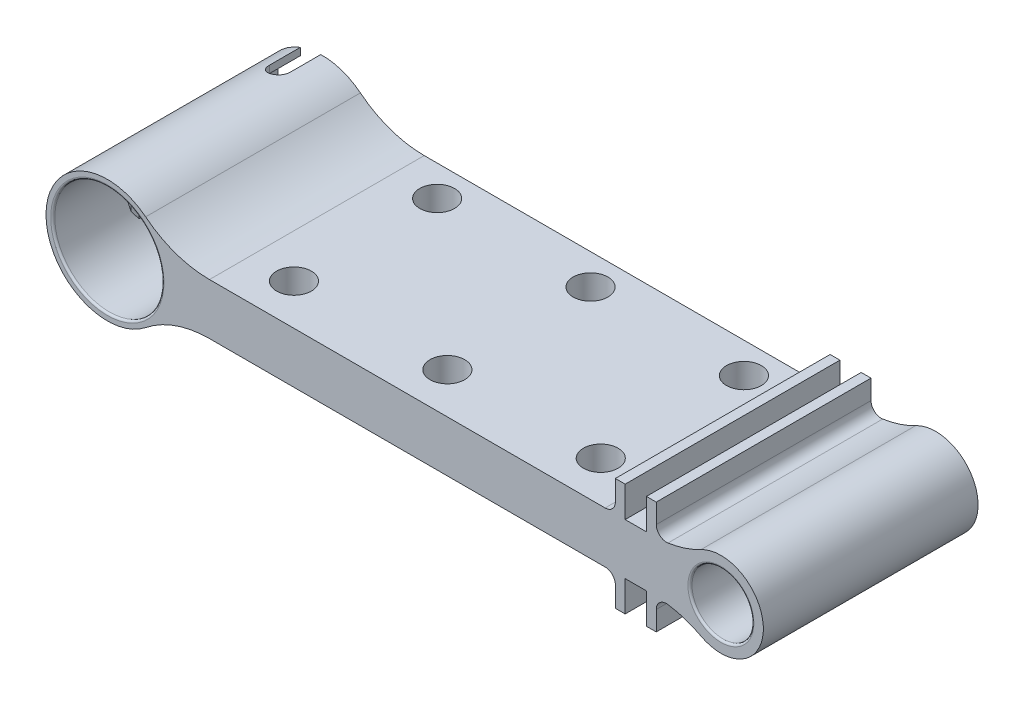
SolidWorks part; units mm, degrees
ref_plane "Front Plane" through (0, 0, 0) normal (0, 0, 1) x (1, 0, 0)
ref_plane "Top Plane" through (0, 0, 0) normal (0, 1, 0) x (1, 0, 0)
ref_plane "Right Plane" through (0, 0, 0) normal (1, 0, 0) x (0, 0, -1)
sketch "Sketch1" plane through (0, 0, 0) normal (0, 0, 1) x (1, 0, 0)
  line L0 (-35, 0) -> (35, 0) construction
  line L1 (35, -6) -> (-35, -6) construction
  line L2 (35, -6) -> (35, 6) construction
  line L3 (35, 6) -> (-35, 6) construction
  line L4 (-35, -6) -> (-35, 6) construction
  line L5 (35, -6) -> (-35, 6) construction
  line L6 (35, 6) -> (-35, -6) construction
  line L8 (-23.4456, -2.5) -> (31.1, -2.5)
  line L10 (-23.4456, 2.5) -> (31.1, 2.5)
  line L12 (-23.1971, -1.8647) -> (31.1, 2.5) construction
  line L13 (-23.1971, 1.8647) -> (31.1, -2.5) construction
  circle A0 centre (-28.9, 0) radius 5.34 construction
  arc A1 (-23.4456, 2.5) -> (-23.4456, -2.5) centre (-28.9, 0) ccw
  arc A2 (31.1, -2.5) -> (31.1, 2.5) centre (31.1, 0) ccw
  point P0 (0, 0)
  point P13 (0, 0)
  dimension "D3" = 10.68
  dimension "D5" = 5
  dimension "D1" = 70
  dimension "D2" = 12
  dimension "D4" = 6.1
  dimension "D6" = 60
extrude "Boss-Extrude1" add sketch "Sketch1" along normal blind 21 contours A1 L8 A2 L10
sketch "Sketch2" plane through (0, 0, 21) normal (0, 0, 1) x (1, 0, 0)
  circle A0 centre (-28.9, 0) radius 5.34
  dimension "D1" = 10.68
extrude "Cut-Extrude1" cut sketch "Sketch2" against normal blind 7
sketch "Sketch3" plane through (0, 0, 14) normal (0, 0, 1) x (1, 0, 0)
  line L0 (-34.24, 0) -> (-23.56, 0) construction
  line L2 (-33.19, -10) -> (-37.19, -10)
  line L3 (-33.19, -10) -> (-33.19, 10)
  line L4 (-33.19, 10) -> (-37.19, 10)
  line L5 (-37.19, -10) -> (-37.19, 10)
  line L6 (-33.19, -10) -> (-37.19, 10) construction
  line L7 (-33.19, 10) -> (-37.19, -10) construction
  line L8 (-20.61, -10) -> (-24.61, -10)
  line L9 (-20.61, -10) -> (-20.61, 10)
  line L10 (-20.61, 10) -> (-24.61, 10)
  line L11 (-24.61, -10) -> (-24.61, 10)
  line L12 (-20.61, -10) -> (-24.61, 10) construction
  line L13 (-20.61, 10) -> (-24.61, -10) construction
  line L14 (-24.61, -10) -> (-33.19, -10) construction
  line L15 (-24.61, -10) -> (-24.61, 10) construction
  line L16 (-24.61, 10) -> (-33.19, 10) construction
  line L17 (-33.19, -10) -> (-33.19, 10) construction
  line L18 (-24.61, -10) -> (-33.19, 10) construction
  line L19 (-24.61, 10) -> (-33.19, -10) construction
  circle A0 centre (-28.9, 0) radius 5.34
  point P5 (-35.19, 0)
  point P10 (-22.61, 0)
  circle M1 centre (-28.9, 0) radius 5.34
  dimension "D6" = 10.68
  dimension "D1" = 20
  dimension "D2" = 4
  dimension "D3" = 4
  dimension "D4" = 8.58
extrude "Cut-Extrude2" cut sketch "Sketch3" against normal through all contours L11 L3 M1 region at (-28.9, 0, 14)
chamfer "Chamfer1" distance 0.4 angle 45 2 edges
fillet "Fillet1" radius 10 2 edges at (-23.4456, -2.5, 10.5) (-23.4456, 2.5, 10.5)
ref_plane "Plane1" through (0, 0, 0) normal (0, 1, 0) x (1, 0, 0)
sketch "Sketch4" plane through (0, 0, 0) normal (0, 1, 0) x (1, 0, 0)
  line L0 (-25.1547, 0) -> (-34.9, 0) construction
  line L1 (-29.0273, -4) -> (-31.0273, -4)
  line L2 (-29.0273, -4) -> (-29.0273, 4)
  line L3 (-29.0273, 4) -> (-31.0273, 4)
  line L4 (-31.0273, -4) -> (-31.0273, 4)
  line L5 (-29.0273, -4) -> (-31.0273, 4) construction
  line L6 (-29.0273, 4) -> (-31.0273, -4) construction
  circle A0 centre (-30.0273, -3) radius 1
  point P0 (-30.0273, 0)
  dimension "D3" = 1
  dimension "D1" = 8
  dimension "D2" = 2
extrude "Cut-Extrude3" cut sketch "Sketch4" along normal mid plane 16.25 contours A0 | A0 L2 L3 L4 region at (-30.0273, 0, 3) region at (-30.0273, 0, -0.8887)
sketch "Sketch6" plane through (0, 0, 21) normal (0, 0, 1) x (1, 0, 0)
  circle A0 centre (31.1, 0) radius 4.15
  dimension "D1" = 8.3
extrude "Boss-Extrude2" add sketch "Sketch6" against normal through all contours A0
fillet "Fillet2" radius 10 2 edges at (27.7875, -2.5, 10.5) (27.7875, 2.5, 10.5)
sketch "Sketch5" plane through (0, 0, 0) normal (0, 0, -1) x (-1, 0, 0)
  circle A0 centre (-31.1, 0) radius 1.5
  circle A2 centre (-6.1, 0) radius 1.5
  circle A3 centre (18.9, 0) radius 1.5
  dimension "D1" = 3
  dimension "D2" = 3
extrude "Cut-Extrude5" cut sketch "Sketch5" against normal blind 4.2
sketch "Sketch7" plane through (0, 0, 21) normal (0, 0, 1) x (1, 0, 0)
  circle A0 centre (31.1, 0) radius 3.025
  dimension "D1" = 6.05
extrude "Cut-Extrude6" cut sketch "Sketch7" against normal blind 9
fillet "Fillet3" radius 0.2 2 edges at (34.125, 0, 21) (-23.56, 0, 21)
sketch "Sketch8" plane through (0, 0, 21) normal (0, 0, 1) x (1, 0, 0)
  line L0 (-18.9125, 2.5) -> (24.4688, 2.5) construction
  line L1 (20.7782, 2.5) -> (24.7782, 2.5) construction
  line L2 (20.7782, 2.5) -> (20.7782, 6.5)
  line L3 (20.7782, 6.5) -> (24.7782, 6.5) construction
  line L4 (24.7782, 2.5) -> (24.7782, 6.5)
  line L5 (22.7782, 6.5) -> (22.7782, 2.5) construction
  line L6 (20.7782, 6.5) -> (21.7382, 6.5)
  line L7 (23.8182, 2.5) -> (21.7382, 2.5) construction
  line L8 (23.8182, 2.5) -> (23.8182, 6.5)
  line L9 (23.8182, 6.5) -> (21.7382, 6.5) construction
  line L10 (21.7382, 2.5) -> (21.7382, 6.5)
  line L11 (23.8182, 2.5) -> (21.7382, 6.5) construction
  line L12 (23.8182, 6.5) -> (21.7382, 2.5) construction
  line L13 (23.8182, 6.5) -> (24.7782, 6.5)
  line L14 (20.7782, 2.5) -> (21.7382, 2.5)
  line L15 (21.7382, 2.5) -> (21.7557, 2.524)
  line L16 (23.8182, 2.5) -> (24.7782, 2.5)
  line L17 (24.7782, 2.5) -> (24.7592, 2.5837)
  line L19 (20.7782, -6.5) -> (20.7782, -2.5)
  line L20 (20.7782, -2.5) -> (21.7382, -2.5)
  line L21 (23.8182, -6.5) -> (23.8182, -2.5)
  line L22 (21.7382, -6.5) -> (21.7382, -2.5)
  line L23 (20.7782, -6.5) -> (21.7382, -6.5)
  line L24 (21.7382, -6.5) -> (21.7557, -6.476)
  line L25 (23.8182, -6.5) -> (24.7782, -6.5)
  line L26 (24.7782, -6.5) -> (24.7592, -6.4163)
  line L27 (20.7782, -6.5) -> (24.7782, -6.5) construction
  line L28 (22.7782, -2.5) -> (22.7782, -6.5) construction
  line L29 (23.8182, -6.5) -> (21.7382, -6.5) construction
  line L30 (23.8182, -2.5) -> (21.7382, -2.5) construction
  line L31 (23.8182, -6.5) -> (21.7382, -2.5) construction
  line L32 (23.8182, -2.5) -> (21.7382, -6.5) construction
  line L33 (23.8182, -2.5) -> (24.7782, -2.5)
  line L34 (24.7782, -6.5) -> (24.7782, -2.5)
  point P8 (2.7782, 2.5)
  point P9 (22.7782, 4.5)
  point P26 (22.7782, -4.5)
  line M3 (-18.9125, -2.5) -> (24.4688, -2.5)
  arc M4 (24.4688, -2.5) -> (29.1552, -3.6661) centre (24.4688, -12.5) cw
  arc M6 (29.1552, 3.6661) -> (24.4688, 2.5) centre (24.4688, 12.5) cw
  line M7 (24.4688, 2.5) -> (-18.9125, 2.5)
  dimension "D3" = 4
  dimension "D1" = 4
  dimension "D2" = 20
  dimension "D4" = 2.08
  dimension "D5" = 2
extrude "Boss-Extrude3" add sketch "Sketch8" against normal through all contours L10 L6 L2 M7 | L13 L8 L4 M7 M6 | L19 L23 L22 M3 | L34 L21 L25 M4 M3 region at (24.2981, 4.5003, 21) region at (21.2582, 4.5, 21) region at (24.2981, -4.5003, 21) region at (21.2582, -4.5, 21)
fillet "Fillet4" radius 1 4 edges at (24.7782, 2.5048, 10.5) (20.7782, 2.5, 10.5) (24.7782, -2.5048, 10.5) (20.7782, -2.5, 10.5)
sketch "Sketch10" plane through (0, 2.5, 0) normal (0, 1, 0) x (1, 0, 0)
  line L0 (-18.9125, -21) -> (19.7782, -21) construction
  line L2 (-14.6488, -17) -> (19.7782, -17) construction
  line L3 (19.7782, -21) -> (19.7782, 0) construction
  circle A0 centre (-14.6488, -17) radius 1.7
  circle A1 centre (0.3512, -17) radius 1.7
  circle A2 centre (15.3512, -17) radius 1.7
  circle A3 centre (0.3512, -3) radius 1.7
  circle A4 centre (15.3512, -3) radius 1.7
  circle A5 centre (-14.6488, -3) radius 1.7
  dimension "D2" = 4
  dimension "D5" = 2
  dimension "D1" = 3.4
  dimension "D4" = 3
extrude "Cut-Extrude7" cut sketch "Sketch10" against normal through all contours A5 | A3 | A1 L2 | L2 A2 | A2 L2 | L2 A1 | A4 | A0 region at (15.3512, 2.5, 16.2785) region at (15.3512, 2.5, 17.7215) region at (0.3512, 2.5, 16.2785) region at (0.3512, 2.5, 17.7215) region at (0.3512, 2.5, 3) region at (15.3512, 2.5, 3) region at (-14.6488, 2.5, 3)
sketch "Sketch12" plane through (0, 0, 21) normal (0, 0, 1) x (1, 0, 0)
  line L0 (24.7782, 3.5958) -> (24.7782, 6.5) construction
  line L1 (20.7782, 6.5) -> (24.7782, 6.5)
  line L2 (20.7782, 6.5) -> (20.7782, 5.5)
  line L3 (20.7782, 5.5) -> (24.7782, 5.5)
  line L4 (24.7782, 6.5) -> (24.7782, 5.5)
  line L5 (24.7782, -6.5) -> (24.7782, -3.5958) construction
  line L6 (20.7782, -6.5) -> (24.7782, -6.5)
  line L7 (20.7782, -6.5) -> (20.7782, -5.5)
  line L8 (20.7782, -5.5) -> (24.7782, -5.5)
  line L9 (24.7782, -6.5) -> (24.7782, -5.5)
  dimension "D1" = 1
  dimension "D2" = 1
extrude "Cut-Extrude8" cut sketch "Sketch12" against normal through all
equation "\"MotorDiameter\"= 10.68'I've added 0.48mm to compesate for my printer tolorance"
equation "\"D3@Sketch1\"=\"MotorDiameter\""
equation "\"D1@Sketch2\"=\"MotorDiameter\""
equation "\"D6@Sketch3\"=\"MotorDiameter\""
equation "\"MotorSlot\"= 8.58 'Ive added 0.48mm to compesate for my printer tolorance"
equation "\"D4@Sketch3\"=\"MotorSlot\""
equation "\"InsertDiameter\"= 6.05 'Ive added 0.48mm to compesate for my printer tolorance"
equation "\"D1@Sketch7\" = \"InsertDiameter\" "
equation "\"GrubScrew\"= 3 'Ive added 0.48mm to compesate for my printer tolorance"
equation "\"D1@Sketch5\"=\"GrubScrew\""
equation "\"PCBThickness\"= 2.08 'Ive added 0.48mm to compesate for my printer tolorance"
equation "\"D4@Sketch8\"=\"PCBThickness\""
equation "\"MountingHoles\"= 3.4 'Ive added 0.4mm to compesate for my printer tolorance"
equation "\"D1@Sketch10\"=\"MountingHoles\""
